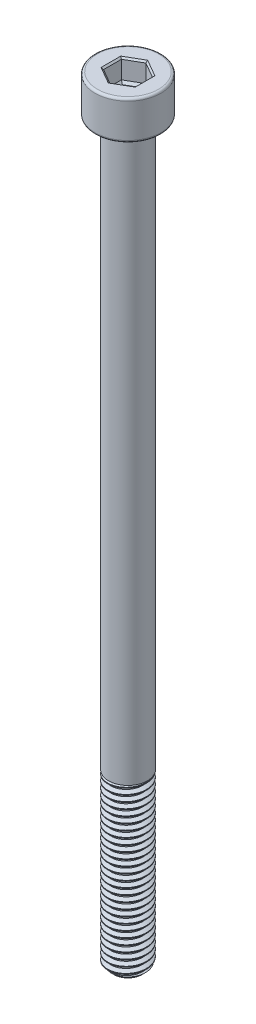
SolidWorks part; units mm, degrees
material "AISI Type A2 Tool Steel"
ref_plane "Front Plane" through (0, 0, 0) normal (0, 0, 1) x (1, 0, 0)
ref_plane "Top Plane" through (0, 0, 0) normal (0, 1, 0) x (1, 0, 0)
ref_plane "Right Plane" through (0, 0, 0) normal (1, 0, 0) x (0, 0, -1)
sketch "Sketch1" plane through (0, 0, 0) normal (0, 1, 0) x (1, 0, 0)
  circle A0 centre (0, 0) radius 2.5
  dimension "D1" = 5
extrude "Boss-Extrude1" add sketch "Sketch1" along normal blind 22
thread "Thread1" pitch 0.8 method cut profile "Thread Profile1" start angle 0, offset 1, length 0, pitch 0.8, diameter 5
ref_plane "Plane1" through (-2.5, 23, 0) normal (0, 0, 1) x (-1, 0, 0)
sketch "Thread Profile1" plane through (-2.5, 23, 0) normal (0, 0, 1) x (-1, 0, 0)
  line L0 (0, 0) -> (0, 0.8) construction
  line L11 (0, 0) -> (0, 0.7)
  line L12 (0, 0.7) -> (-0.433, 0.45)
  line L13 (-0.433, 0.45) -> (-0.433, 0.25)
  line L15 (-0.433, 0.25) -> (0, 0)
  line L17 (-0.433, 0.35) -> (0, 0.35) construction
  point P2 (0, 0)
  dimension "Pitch" = 0.8
  dimension "Profile_Angle" = 60
  dimension "Profile_Land" = 0.2
  dimension "Profile_Height" = 0.433
sketch "Sketch2" plane through (0, 22, 0) normal (0, 1, 0) x (1, 0, 0)
  circle A0 centre (0, 0) radius 2.5
  dimension "D1" = 5
extrude "Boss-Extrude2" add sketch "Sketch2" along normal blind 73
sketch "Sketch3" plane through (0, 95, 0) normal (0, 1, 0) x (1, 0, 0)
  circle A0 centre (0, 0) radius 4.25
  dimension "D1" = 8.5
extrude "Boss-Extrude3" add sketch "Sketch3" along normal blind 5
fillet "Fillet1" radius 0.3 2 edges at (0, 95, 4.25) (0, 100, 4.25)
sketch "Sketch4" plane through (0, 0, 0) normal (0, 0, 1) x (1, 0, 0)
  line L0 (0, 0) -> (0, 0.4416) construction
  line L1 (0, 0) -> (2.51, 0) construction
  line L2 (2.51, 0) -> (2.51, 0.7)
  line L3 (2.51, 0.7) -> (1.81, 0)
  line L4 (1.81, 0) -> (2.51, 0)
  dimension "D1" = 0.7
  dimension "D2" = 45
  dimension "D3" = 2.51
revolve "Cut-Revolve1" cut sketch "Sketch4" angle 360 about L0
sketch "Sketch5" plane through (0, 100, 0) normal (0, 1, 0) x (1, 0, 0)
  line L1 (0, 2.3094) -> (-2, 1.1547)
  line L2 (-2, 1.1547) -> (-2, -1.1547)
  line L3 (-2, -1.1547) -> (0, -2.3094)
  line L4 (0, -2.3094) -> (2, -1.1547)
  line L5 (2, -1.1547) -> (2, 1.1547)
  line L6 (2, 1.1547) -> (0, 2.3094)
  circle A0 centre (0, 0) radius 2 construction
  dimension "D1" = 4
extrude "Cut-Extrude1" cut sketch "Sketch5" against normal blind 2.5
chamfer "Chamfer1" distance 0.2 angle 45 6 edges at (-1, 100, 1.7321) (1, 100, 1.7321) (2, 100, 0) (1, 100, -1.7321) (-1, 100, -1.7321) (-2, 100, 0)
sketch "Sketch6" plane through (0, 97.5, 0) normal (0, 1, 0) x (1, 0, 0)
  line L1 (0, 2.3094) -> (-2, 1.1547)
  line L2 (-2, 1.1547) -> (-2, -1.1547)
  line L3 (-2, -1.1547) -> (0, -2.3094)
  line L4 (0, -2.3094) -> (2, -1.1547)
  line L5 (2, -1.1547) -> (2, 1.1547)
  line L6 (2, 1.1547) -> (0, 2.3094)
  circle A0 centre (0, 0) radius 2 construction
extrude "Cut-Extrude2" cut sketch "Sketch6" against normal blind 0.3 draft 45
